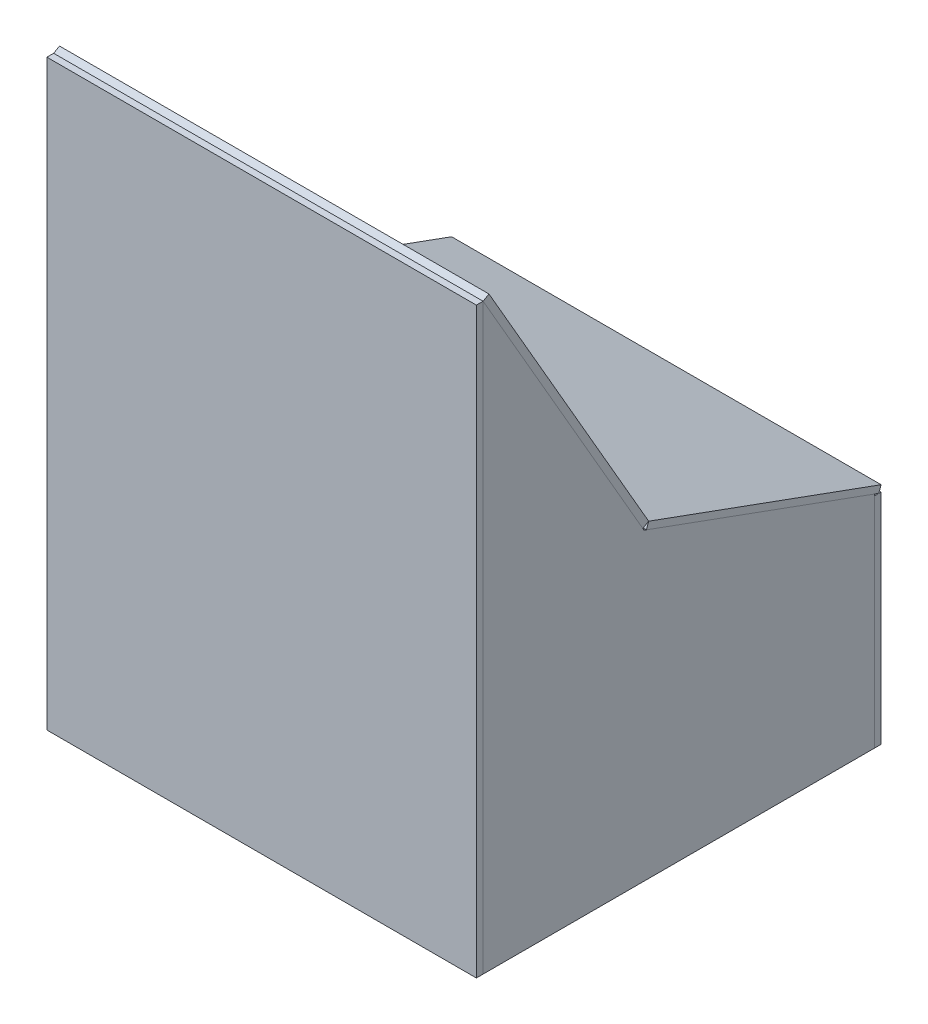
SolidWorks part; units mm, degrees
note: The reader was unsure of these and kept them because the rebuilt part matched: shared geometry of "Esquisse10<3>".
ref_plane "Plan de face" through (0, 0, 0) normal (0, 0, 1) x (1, 0, 0)
ref_plane "Plan de dessus" through (0, 0, 0) normal (0, 1, 0) x (1, 0, 0)
ref_plane "Plan de droite" through (0, 0, 0) normal (1, 0, 0) x (0, 0, -1)
sketch "repere_profil" plane through (0, 0, 0) normal (1, 0, 0) x (0, 0, -1)
  line L0 (0, 0) -> (-180, 0)
  line L1 (-180, 0) -> (-180, 259.1597)
  line L3 (0, 100) -> (0, 0)
  line L4 (-3, 3) -> (-177, 3)
  line L5 (-177, 3) -> (-177, 259.1597)
  line L7 (-3, 97.8994) -> (-3, 3)
  line L8 (-3, 87.2576) -> (-4.0261, 87.6311) construction
  line L9 (-105.4183, 124.5348) -> (-105.4183, 135.1766)
  line L10 (-177, 259.1597) -> (-180, 259.1597)
  line L11 (-3, 97.8994) -> (-1.0261, 97.1809) construction
  line L12 (-1.0261, 97.1809) -> (0, 100) construction
  line L13 (-3, 97.1809) -> (0, 97.1809) construction
  line L14 (-3, 3) -> (-3, 0) construction
  line L15 (-177, 3) -> (-177, 0) construction
  line L16 (-105.4183, 135.1766) -> (-3, 97.8994)
  line L17 (-177, 161.2302) -> (-3, 97.8994) construction
  line L18 (-103.3662, 137.6222) -> (0, 100)
  line L19 (-180, 165.5146) -> (0, 100) construction
  line L20 (-105.4183, 135.1766) -> (-177, 259.1597)
  line L21 (-103.3662, 137.6222) -> (-174.4019, 260.6597)
  line L22 (-177, 259.1597) -> (-174.4019, 260.6597)
  line L23 (-180, 0) -> (-180, 165.5146) construction
  line L24 (-177, 3) -> (-177, 161.2302) construction
  line L25 (-4.0261, 87.6311) -> (-105.4183, 124.5348)
  line L26 (-4.0261, 87.6311) -> (-3, 90.4501)
  line L27 (-3, 90.4501) -> (-104.3922, 127.3539)
  line L28 (-104.3922, 127.3539) -> (-105.4183, 124.5348)
  point P10 (0, 0)
  point P21 (0, 0)
  point P25 (0, 0)
  point P26 (0, 0)
  dimension "D2" = 100
  dimension "D3" = 180
  dimension "D4" = 70
  dimension "D5" = 30
  dimension "D6" = 110
  dimension "D7" = 10
  dimension "D8" = 142.0715
  dimension "D9" = 259.1597
  dimension "D1" = 3
sketch "repere_face_panneau" plane through (0, 0, 0) normal (0, 1, 0) x (1, 0, 0)
  line L0 (-188, -140) -> (-142, -140) construction
  line L1 (-142, -140) -> (-71, -140) construction
  line L2 (-71, -140) -> (0, -140) construction
  line L3 (0, -140) -> (71, -140) construction
  line L4 (71, -140) -> (142, -140) construction
  line L5 (142, -140) -> (188, -140) construction
  line L6 (0, -140) -> (0, 0) construction
  line L7 (-188, -140) -> (-191, -140) construction
  line L8 (188, -140) -> (191, -140) construction
  line L9 (-106.5, -140) -> (-106.5, 0) construction
  line L10 (-35.5, -140) -> (-35.5, 0) construction
  line L11 (35.5, -140) -> (35.5, 0) construction
  line L12 (106.5, -140) -> (106.5, 0) construction
  point P19 (0, 0)
  point P20 (0, 0)
  point P21 (0, 0)
  dimension "D1" = 140
  dimension "D2" = 71
  dimension "D3" = 46
  dimension "D4" = 376
  dimension "D5" = 3
ref_plane "Plan_panneau" through (0, -11.8533, 20.5305) normal (0, 0.5, -0.866) x (0, 0.866, 0.5)
ref_plane "Plan_tablette" through (0, 85.4831, -31.1133) normal (0, -0.9397, 0.342) x (0, -0.342, -0.9397)
ref_plane "Plan_support_tablette" through (0, 78.9053, -28.7192) normal (0, -0.9397, 0.342) x (-1, 0, 0)
ref_plane "Plan_arriere" through (0, 0, 180) normal (0, 0, 1) x (1, 0, 0)
sketch "Esquisse3" plane through (0, 0, 0) normal (0, 1, 0) x (1, 0, 0)
  line L1 (188, -3) -> (0, -3)
  line L2 (188, -3) -> (188, -177)
  line L3 (188, -177) -> (0, -177)
  line L4 (0, -3) -> (0, -177)
extrude "plq_base" add sketch "Esquisse3" along normal blind 3
sketch "Esquisse4" plane through (0, 0, 180) normal (0, 0, 1) x (1, 0, 0)
  line L1 (0, 259.1597) -> (191, 259.1597)
  line L2 (0, 259.1597) -> (0, 0)
  line L3 (0, 0) -> (191, 0)
  line L4 (191, 259.1597) -> (191, 0)
extrude "plq_arriere" add sketch "Esquisse4" against normal blind 3 separate body
sketch "Esquisse5" plane through (0, 0, 0) normal (0, 0, 1) x (1, 0, 0)
  line L1 (0, 97.1809) -> (191, 97.1809)
  line L2 (0, 97.1809) -> (0, 0)
  line L3 (0, 0) -> (191, 0)
  line L4 (191, 97.1809) -> (191, 0)
extrude "plq_avant" add sketch "Esquisse5" along normal blind 3 separate body
sketch "Esquisse6" plane through (0, -11.8533, 20.5305) normal (0, 0.5, -0.866) x (0, 0.866, 0.5)
  line L1 (312.9389, 0) -> (170.8674, 0)
  line L2 (312.9389, 0) -> (312.9389, 191)
  line L3 (312.9389, 191) -> (170.8674, 191)
  line L4 (170.8674, 0) -> (170.8674, 191)
extrude "plq_panneau (dessus)" add sketch "Esquisse6" along normal blind 3 separate body
sketch "Esquisse11" plane through (0, 85.4831, -31.1133) normal (0, -0.9397, 0.342) x (0, -0.342, -0.9397)
  line L1 (-144.202, 0) -> (-34.202, 0)
  line L2 (-144.202, 0) -> (-144.202, 191)
  line L3 (-144.202, 191) -> (-34.202, 191)
  line L4 (-34.202, 0) -> (-34.202, 191)
  point P4 (-110, 140.3959)
extrude "plq_tablette" add sketch "Esquisse11" against normal blind 3 separate body
sketch "Esquisse7" plane through (0, 0, 0) normal (1, 0, 0) x (0, 0, -1)
  line L0 (-177, 259.1597) -> (-177, 0)
  line L1 (-177, 0) -> (-3, 0)
  line L2 (-3, 0) -> (-3, 97.8994)
  line L3 (-3, 97.8994) -> (-105.4183, 135.1766)
  line L4 (-105.4183, 135.1766) -> (-177, 259.1597)
  point P3 (-113.7635, 138.214)
  point P9 (-105.4183, 135.1766)
extrude "plq_cote" add sketch "Esquisse7" against normal blind 3 from vertex at 191 separate body starting at point (191, 0, 140)
sketch "Esquisse9" plane through (0, -11.8533, 20.5305) normal (0, 0.5, -0.866) x (0, 0.866, 0.5)
  line L0 (70, 142) -> (277.9389, 142) construction
  line L5 (312.9389, 0) -> (312.9389, 191) construction
  circle A4 centre (277.9389, 142) radius 22.5
  dimension "D1" = 45
  dimension "D2" = 35
extrude "fente_1" cut sketch "Esquisse9" along normal through all
pattern_linear "Répétition linéaire2" count 3 spacing 71 along (-1, 0, 0) of "fente_1"
sketch "Esquisse10" plane through (0, 0, 0) normal (1, 0, 0) x (0, 0, -1)
  line L0 (-177, 259.1597) -> (-177, 3)
  line L1 (-177, 3) -> (-3, 3)
  line L2 (-3, 3) -> (-3, 87.2576)
  line L3 (-3, 87.2576) -> (-105.4183, 124.5348)
  line L6 (-155.6325, 210.1502) -> (-150.4364, 213.1502)
  line L7 (-150.4364, 213.1502) -> (-177, 259.1597)
  line L8 (-150.4364, 213.1502) -> (-108.4183, 140.3727) construction
  line L9 (-177, 173.7731) -> (-180, 173.7731)
  line L10 (-113.6145, 137.3727) -> (-155.6325, 210.1502)
  line L12 (-108.4183, 140.3727) -> (-105.4183, 135.1766)
  line L13 (-105.4183, 135.1766) -> (-3, 97.8994) construction
  line L14 (-113.6145, 137.3727) -> (-108.4183, 140.3727)
  line L16 (-177, 239.1597) -> (-180, 239.1597)
  line L17 (-180, 239.1597) -> (-180, 219.1597)
  line L18 (-180, 219.1597) -> (-177, 219.1597)
  line L19 (-177, 43) -> (-180, 43)
  line L20 (-180, 43) -> (-180, 23)
  line L21 (-180, 23) -> (-177, 23)
  line L22 (-157, 3) -> (-157, 0)
  line L23 (-157, 0) -> (-137, 0)
  line L24 (-137, 0) -> (-137, 3)
  line L25 (-43, 3) -> (-43, 0)
  line L26 (-43, 0) -> (-23, 0)
  line L27 (-23, 0) -> (-23, 3)
  line L28 (-3, 8) -> (0, 8)
  line L29 (0, 8) -> (0, 18)
  line L30 (0, 18) -> (-3, 18)
  line L31 (-3, 72.2576) -> (0, 72.2576)
  line L32 (0, 72.2576) -> (0, 82.2576)
  line L33 (0, 82.2576) -> (-3, 82.2576)
  line L34 (-137, 0) -> (-43, 0) construction
  line L35 (-90, 0) -> (-90, 3) construction
  line L36 (0, 72.2576) -> (0, 18) construction
  line L37 (0, 45.1288) -> (-3, 45.1288) construction
  line L38 (-180, 173.7731) -> (-180, 153.7731)
  line L39 (-180, 131.0799) -> (-177, 131.0799) construction
  line L40 (-105.4183, 135.1766) -> (-105.4183, 124.5348)
  line L42 (-103.3662, 137.6222) -> (0, 100) construction
  line L43 (0, 100) -> (0, 0) construction
  line L44 (-180, 153.7731) -> (-177, 153.7731)
  line L45 (-83.4709, 116.5466) -> (-82.4448, 119.3657)
  line L46 (-82.4448, 119.3657) -> (-63.651, 112.5253)
  line L47 (-63.651, 112.5253) -> (-64.6771, 109.7062)
  line L48 (-50.5817, 104.5759) -> (-49.5556, 107.395)
  line L49 (-49.5556, 107.395) -> (-30.7617, 100.5546)
  line L50 (-30.7617, 100.5546) -> (-31.7878, 97.7355)
  line L51 (-63.651, 112.5253) -> (-49.5556, 107.395) construction
  line L52 (-56.6033, 109.9601) -> (-54.2092, 116.538) construction
  line L56 (-177, 108.3866) -> (-180, 108.3866)
  line L57 (-180, 108.3866) -> (-180, 88.3866)
  line L58 (-180, 88.3866) -> (-177, 88.3866)
  line L59 (-180, 108.3866) -> (-180, 153.7731) construction
  line L60 (-180, 173.7731) -> (-180, 219.1597) construction
  line L61 (-180, 88.3866) -> (-180, 43) construction
  line L62 (-105.4183, 135.1766) -> (-177, 259.1597) construction
  point P46 (-147, 0)
  point P47 (0, 13)
  point P54 (-180, 33)
  point P55 (-145.453, 204.5187)
  point P58 (-73.0479, 115.9455)
  point P59 (-40.1587, 103.9748)
  point P61 (-150.4364, 213.1443)
  point P71 (0, 0)
  point P74 (0, 0)
  point P81 (0, 0)
  point P82 (0, 0)
  point P83 (-135.5287, 187.3293)
  dimension "D2" = 6
  dimension "D5" = 6
  dimension "D6" = 10
  dimension "D7" = 30
  dimension "D8" = 20
  dimension "D9" = 10
  dimension "D10" = 30
  dimension "D11" = 35
extrude "separateur_1" add sketch "Esquisse10" along normal mid plane 3 from vertex at 106.5 separate body
extrude "separateur_2" add sketch "Esquisse10<3>" along normal mid plane 3 from vertex at 35.5 separate body contours L40 L12 L14 L10 L6 L7 L0 L1 L2 L3 | L47 L46 L45 L3 | L32 L33 L2 L31 | L29 L30 L2 L28 | L26 L27 L1 L25 | L23 L24 L1 L22 | L20 L21 L0 L19 | L57 L58 L0 L56 | L38 L44 L0 L9 | L17 L18 L0 L16 | L50 L49 L48 L3 starting at point (35.5, 0, 140)
sketch "Esquisse10<3>" plane through (0, 0, 0) normal (1, 0, 0) x (0, 0, -1) same geometry as "Esquisse10"
sketch "Esquisse13" plane through (0, 78.9053, -28.7192) normal (0, -0.9397, 0.342) x (-1, 0, 0)
  line L1 (-188, -33.7548) -> (0, -33.7548)
  line L2 (-188, -33.7548) -> (-188, -141.6542)
  line L3 (-188, -141.6542) -> (0, -141.6542)
  line L4 (0, -33.7548) -> (0, -141.6542)
extrude "plq support tablette" add sketch "Esquisse13" along normal blind 3 separate body
equation "\"ep_plexi\"=3"
equation "\"D5@repere_face_panneau\"=\"ep_plexi\""
equation "\"D1@repere_profil\"=\"ep_plexi\""
equation "\"D1@plq_base\"=\"ep_plexi\""
equation "\"D1@plq_arriere\" = \"ep_plexi\""
equation "\"D1@plq_avant\" = \"ep_plexi\""
equation "\"D1@plq_panneau (dessus)\" = \"ep_plexi\""
equation "\"D1@plq_cote\" = \"ep_plexi\""
equation "\"D1\" = \"ep_plexi\""
equation "\"D1@plq_tablette\" = \"ep_plexi\""
equation "\"D1@plq support tablette\" = \"ep_plexi\""
equation "\"D1@separateur_2\"=\"ep_plexi\""
